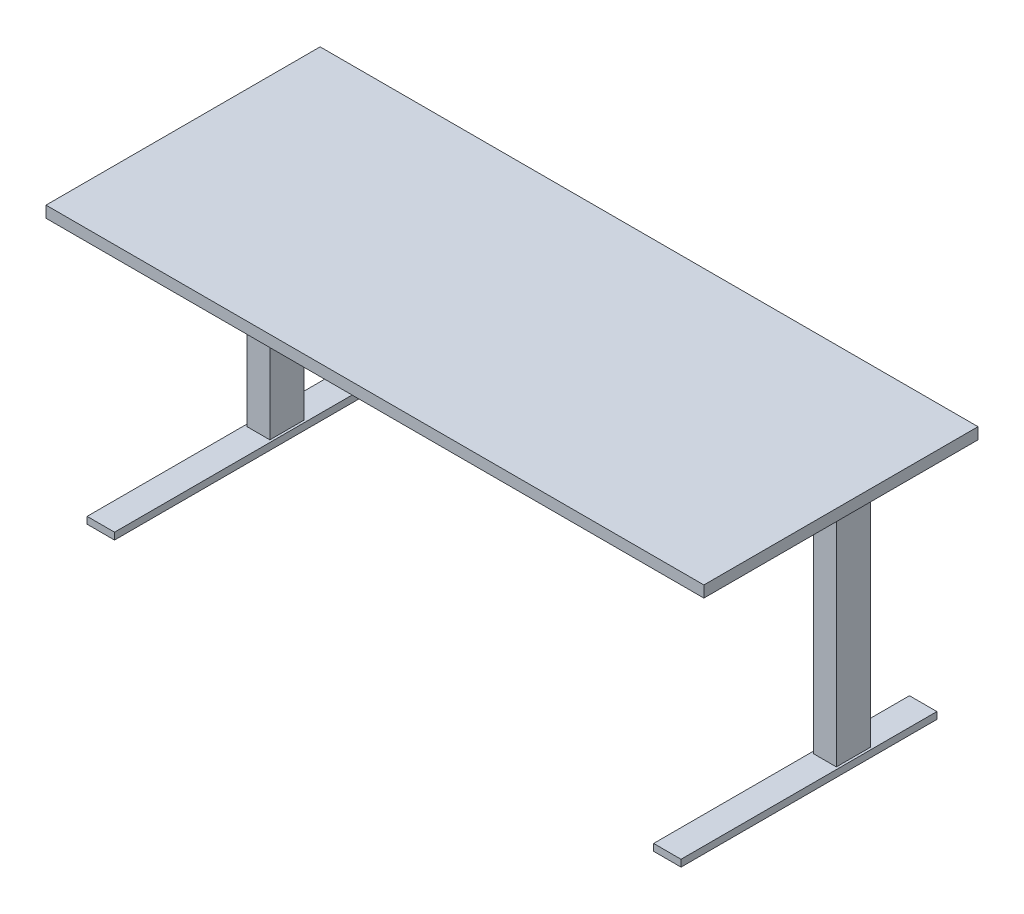
SolidWorks part; units mm, degrees
material "Plain Carbon Steel"
ref_plane "Front Plane" through (0, 0, 0) normal (0, 0, 1) x (1, 0, 0)
ref_plane "Top Plane" through (0, 0, 0) normal (0, 1, 0) x (1, 0, 0)
ref_plane "Right Plane" through (0, 0, 0) normal (1, 0, 0) x (0, 0, -1)
sketch "Sketch1" plane through (0, 0, 0) normal (0, 1, 0) x (1, 0, 0)
  line L1 (-914.4, -381) -> (914.4, -381)
  line L2 (-914.4, -381) -> (-914.4, 381)
  line L3 (-914.4, 381) -> (914.4, 381)
  line L4 (914.4, -381) -> (914.4, 381)
  line L5 (-914.4, -381) -> (914.4, 381) construction
  line L6 (-914.4, 381) -> (914.4, -381) construction
  point P0 (0, 0)
  dimension "D1" = 762
  dimension "D2" = 1828.8
extrude "Boss-Extrude1" add sketch "Sketch1" against normal blind 31.75
sketch "Sketch2" plane through (0, -31.75, 0) normal (0, -1, 0) x (1, 0, 0)
  line L0 (914.4, -381) -> (-914.4, -381) construction
  line L1 (-850.9, -279.4) -> (-819.15, -279.4)
  line L2 (-850.9, -279.4) -> (-850.9, -38.1)
  line L3 (-850.9, -38.1) -> (-819.15, -38.1)
  line L4 (-819.15, -279.4) -> (-819.15, -38.1)
  line L5 (-914.4, -381) -> (-914.4, 381) construction
  dimension "D1" = 101.6
  dimension "D2" = 241.3
  dimension "D3" = 31.75
  dimension "D4" = 63.5
extrude "Boss-Extrude2" add sketch "Sketch2" along normal blind 50.8
sketch "Sketch3" plane through (0, -31.75, 0) normal (0, -1, 0) x (1, 0, 0)
  line L0 (914.4, -381) -> (-914.4, -381) construction
  line L1 (-819.15, -177.8) -> (-755.65, -177.8)
  line L2 (-819.15, -177.8) -> (-819.15, -82.55)
  line L3 (-819.15, -82.55) -> (-755.65, -82.55)
  line L4 (-755.65, -177.8) -> (-755.65, -82.55)
  line L5 (-819.15, -279.4) -> (-819.15, -38.1) construction
  dimension "D1" = 203.2
  dimension "D2" = 95.25
  dimension "D3" = 63.5
extrude "Boss-Extrude3" add sketch "Sketch3" along normal blind 685.8
sketch "Sketch4" plane through (0, -717.55, 0) normal (0, -1, 0) x (1, 0, 0)
  line L0 (-755.65, -82.55) -> (-819.15, -82.55) construction
  line L1 (-825.5, -355.6) -> (-749.3, -355.6)
  line L2 (-825.5, -355.6) -> (-825.5, 355.6)
  line L3 (-825.5, 355.6) -> (-749.3, 355.6)
  line L4 (-749.3, -355.6) -> (-749.3, 355.6)
  line L5 (-825.5, -355.6) -> (-749.3, 355.6) construction
  line L6 (-825.5, 355.6) -> (-749.3, -355.6) construction
  point P0 (-787.4, 0)
  point P7 (-787.4, -82.55)
  dimension "D1" = 76.2
  dimension "D2" = 711.2
extrude "Boss-Extrude4" add sketch "Sketch4" along normal offset from surface (19.05 mm away) 736.6 up to face at (0, 0, 0)
mirror "Mirror1" about plane through (0, 0, 0) normal (1, 0, 0) of "Boss-Extrude4", "Boss-Extrude3", "Boss-Extrude2"
